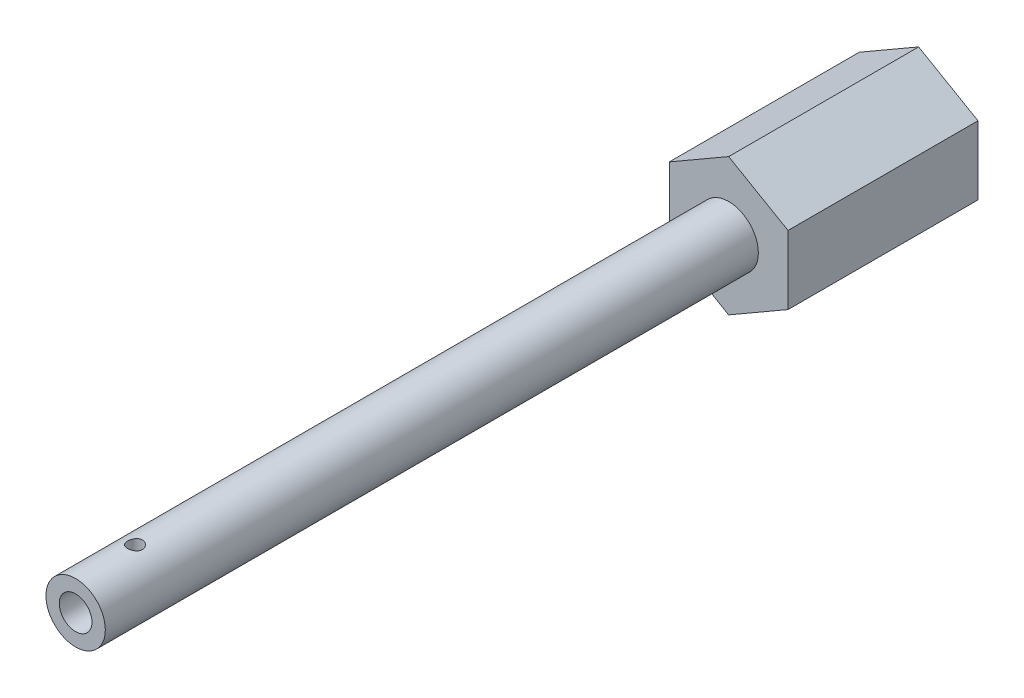
SolidWorks part; units mm, degrees
ref_plane "Front Plane" through (0, 0, 0) normal (0, 0, 1) x (1, 0, 0)
ref_plane "Top Plane" through (0, 0, 0) normal (0, 1, 0) x (1, 0, 0)
ref_plane "Right Plane" through (0, 0, 0) normal (1, 0, 0) x (0, 0, -1)
sketch "Sketch1" plane through (0, 0, 0) normal (0, 0, 1) x (1, 0, 0)
  line L1 (0, 7.3323) -> (-6.35, 3.6662)
  line L2 (-6.35, 3.6662) -> (-6.35, -3.6662)
  line L3 (-6.35, -3.6662) -> (0, -7.3323)
  line L4 (0, -7.3323) -> (6.35, -3.6662)
  line L5 (6.35, -3.6662) -> (6.35, 3.6662)
  line L6 (6.35, 3.6662) -> (0, 7.3323)
  circle A0 centre (0, 0) radius 6.35 construction
  dimension "D1" = 12.7
extrude "Boss-Extrude1" add sketch "Sketch1" along normal blind 20.32 contours L6 L1 L2 L3 L4 L5
sketch "Sketch2" plane through (0, 0, 20.32) normal (0, 0, 1) x (1, 0, 0)
  circle A0 centre (0, 0) radius 3.175
  dimension "D1" = 6.35
extrude "Boss-Extrude2" add sketch "Sketch2" along normal blind 69.85
hole_wizard "Ø3.5 (3.5) Diameter Hole1" positions "Sketch3" profile "Sketch4" hole size "Ø3.5" standard "ANSI Metric"
sketch "Sketch3" plane through (0, 0, 90.17) normal (0, 0, 1) x (1, 0, 0)
  point P0 (0, 0)
sketch "Sketch4" plane through (0, 0, 90.17) normal (1, 0, 0) x (0, -1, 0)
  line L0 (0, 0) -> (0, 26.4515)
  line L1 (0, 26.4515) -> (1.75, 25.4)
  line L2 (1.75, 25.4) -> (1.75, 0)
  line L5 (1.75, 0) -> (0, 0)
  line L10 (0, 26.4515) -> (-1.75, 25.4) construction
  line L11 (0, -6.35) -> (0, 107.95) construction
  dimension "Hole Dia." = 3.5
  dimension "Hole Depth" = 25.4
  dimension "Drill Angle" = 118
ref_plane "Plane1" through (0, 7.62, 0) normal (0, 1, 0) x (1, 0, 0)
hole_wizard "1/16 (0.0625) Diameter Hole1" positions "Sketch5" profile "Sketch6" hole size "1/16" standard "ANSI Inch" end condition through all
sketch "Sketch5" plane through (0, 7.62, 0) normal (0, 1, 0) x (1, 0, 0)
  line L0 (-3.175, -90.17) -> (3.175, -90.17) construction
  point P0 (0, -83.82)
  dimension "D1" = 6.35
sketch "Sketch6" plane through (0, 7.62, 83.82) normal (1, 0, 0) x (0, 0, 1)
  line L0 (0, 0) -> (0, 14.9523)
  line L1 (0, 14.9523) -> (0.7937, 14.9523)
  line L2 (0.7937, 14.9523) -> (0.7937, 0)
  line L5 (0.7937, 0) -> (0, 0)
  line L11 (0, -6.35) -> (0, 107.95) construction
  dimension "Thru Hole Dia." = 1.5875
  dimension "Thru Hole Depth" = 14.9523
